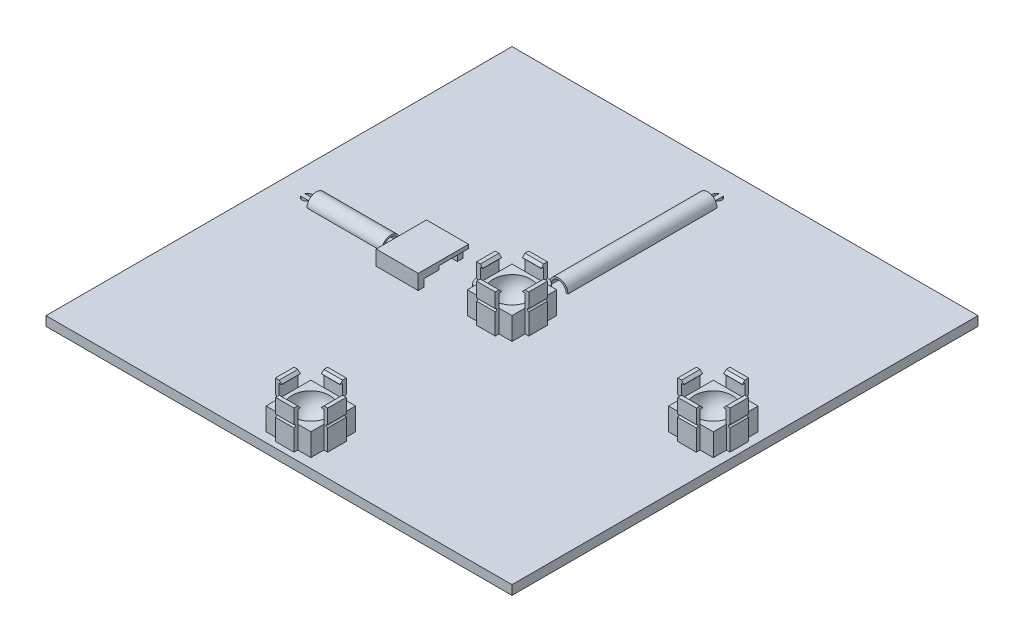
SolidWorks part; units mm, degrees
ref_plane "Front Plane" through (0, 0, 0) normal (0, 0, 1) x (1, 0, 0)
ref_plane "Top Plane" through (0, 0, 0) normal (0, 1, 0) x (1, 0, 0)
ref_plane "Right Plane" through (0, 0, 0) normal (1, 0, 0) x (0, 0, -1)
sketch "Sketch1" plane through (0, 0, 0) normal (0, 1, 0) x (1, 0, 0)
  line L1 (0, 0) -> (250, 0)
  line L2 (0, 0) -> (0, 250)
  line L3 (0, 250) -> (250, 250)
  line L4 (250, 0) -> (250, 250)
  dimension "D1" = 250
  dimension "D2" = 250
extrude "Boss-Extrude1" add sketch "Sketch1" along normal blind 5
sketch "Sketch2" plane through (0, 5, 0) normal (0, 1, 0) x (1, 0, 0)
  line L1 (113, 113) -> (137, 113)
  line L2 (113, 113) -> (113, 137)
  line L3 (113, 137) -> (137, 137)
  line L4 (137, 113) -> (137, 137)
  line L5 (113, 113) -> (137, 137) construction
  line L6 (113, 137) -> (137, 113) construction
  line L7 (0, 250) -> (0, 0) construction
  line L8 (250, 250) -> (0, 250) construction
  line L10 (221, 137) -> (221, 113)
  line L11 (221, 113) -> (245, 113)
  line L12 (245, 113) -> (245, 137)
  line L13 (245, 137) -> (221, 137)
  line L19 (137, 29.0789) -> (113, 29.0789)
  line L20 (113, 29.0789) -> (113, 5.0789)
  line L21 (113, 5.0789) -> (137, 5.0789)
  line L22 (137, 5.0789) -> (137, 29.0789)
  point P0 (125, 125)
  dimension "D1" = 24
  dimension "D2" = 24
  dimension "D3" = 125
  dimension "D4" = 125
extrude "Boss-Extrude2" add sketch "Sketch2" along normal blind 12
sketch "Sketch4" plane through (0, 17, 0) normal (0, 1, 0) x (1, 0, 0)
  line L0 (125, 135) -> (125, 115)
  line L1 (125, 7) -> (125, 27)
  line L3 (233, 135) -> (233, 115)
  arc A0 (125, 135) -> (125, 115) centre (125, 125) ccw
  arc A2 (125, 27) -> (125, 7) centre (125, 17) ccw
  arc A3 (233, 115) -> (233, 135) centre (233, 125) ccw
revolve "Cut-Revolve1" cut sketch "Sketch4" angle 360 about L0 region at (120.7559, 17, -125)
revolve "Cut-Revolve2" cut sketch "Sketch4<3>" angle 360 about L3
sketch "Sketch4<3>" plane through (0, 17, 0) normal (0, 1, 0) x (1, 0, 0) same geometry as "Sketch4"
revolve "Cut-Revolve3" cut sketch "Sketch4<4>" angle 360 about L1
sketch "Sketch4<4>" plane through (0, 17, 0) normal (0, 1, 0) x (1, 0, 0) same geometry as "Sketch4"
sketch "Sketch5" plane through (0, 5, 0) normal (0, 1, 0) x (1, 0, 0)
  line L8 (125, 137) -> (130, 137)
  line L9 (137, 137) -> (113, 137) construction
  line L10 (137, 137) -> (113, 137) construction
  line L11 (130, 137) -> (130, 139)
  line L12 (130, 139) -> (120, 139)
  line L13 (120, 139) -> (120, 137)
  line L14 (120, 137) -> (125, 137)
  line L15 (120, 113) -> (125, 113)
  line L16 (120, 111) -> (120, 113)
  line L17 (130, 111) -> (120, 111)
  line L18 (130, 113) -> (130, 111)
  line L19 (125, 113) -> (130, 113)
  line L21 (113, 29.0789) -> (113, 5.0789) construction
  line L22 (137, 5.0789) -> (137, 29.0789) construction
  line L24 (125, 29.0789) -> (130, 29.0789)
  line L25 (130, 29.0789) -> (130, 31.0789)
  line L26 (130, 31.0789) -> (120, 31.0789)
  line L27 (120, 31.0789) -> (120, 29.0789)
  line L28 (120, 29.0789) -> (125, 29.0789)
  line L29 (120, 5.0789) -> (125, 5.0789)
  line L30 (120, 3.0789) -> (120, 5.0789)
  line L31 (130, 3.0789) -> (120, 3.0789)
  line L32 (130, 5.0789) -> (130, 3.0789)
  line L33 (125, 5.0789) -> (130, 5.0789)
  line L36 (113, 130) -> (113, 125)
  line L37 (111, 130) -> (113, 130)
  line L38 (111, 120) -> (111, 130)
  line L39 (113, 120) -> (111, 120)
  line L40 (113, 125) -> (113, 120)
  line L41 (137, 125) -> (137, 120)
  line L42 (137, 120) -> (139, 120)
  line L43 (139, 120) -> (139, 130)
  line L44 (139, 130) -> (137, 130)
  line L45 (137, 130) -> (137, 125)
  line L46 (220.9211, 130) -> (220.9211, 125)
  line L47 (218.9211, 130) -> (220.9211, 130)
  line L48 (218.9211, 120) -> (218.9211, 130)
  line L49 (220.9211, 120) -> (218.9211, 120)
  line L50 (220.9211, 125) -> (220.9211, 120)
  line L51 (244.9211, 125) -> (244.9211, 120)
  line L52 (244.9211, 120) -> (246.9211, 120)
  line L53 (246.9211, 120) -> (246.9211, 130)
  line L54 (246.9211, 130) -> (244.9211, 130)
  line L55 (244.9211, 130) -> (244.9211, 125)
  line L56 (137, 12.0789) -> (137, 17.0789)
  line L57 (139, 12.0789) -> (137, 12.0789)
  line L58 (139, 22.0789) -> (139, 12.0789)
  line L59 (137, 22.0789) -> (139, 22.0789)
  line L60 (137, 17.0789) -> (137, 22.0789)
  line L61 (113, 17.0789) -> (113, 22.0789)
  line L62 (113, 22.0789) -> (111, 22.0789)
  line L63 (111, 22.0789) -> (111, 12.0789)
  line L64 (111, 12.0789) -> (113, 12.0789)
  line L65 (113, 12.0789) -> (113, 17.0789)
  line L66 (237.9211, 137) -> (232.9211, 137)
  line L67 (237.9211, 139) -> (237.9211, 137)
  line L68 (227.9211, 139) -> (237.9211, 139)
  line L69 (227.9211, 137) -> (227.9211, 139)
  line L70 (232.9211, 137) -> (227.9211, 137)
  line L71 (232.9211, 113) -> (227.9211, 113)
  line L72 (227.9211, 113) -> (227.9211, 111)
  line L73 (227.9211, 111) -> (237.9211, 111)
  line L74 (237.9211, 111) -> (237.9211, 113)
  line L75 (237.9211, 113) -> (232.9211, 113)
extrude "Boss-Extrude3" add sketch "Sketch5" along normal blind 19
sketch "Sketch8" plane through (120, 0, 0) normal (-1, 0, 0) x (0, 0, 1)
  line L0 (-3.0789, 24) -> (-6.5789, 24)
  line L1 (-3.0789, 24) -> (-3.0789, 25.5)
  line L2 (-3.0789, 25.5) -> (-5.0789, 25.5)
  line L3 (-5.0789, 25.5) -> (-6.5789, 24)
  line L8 (-29.0789, 25.5) -> (-27.5789, 24)
  line L9 (-31.0789, 25.5) -> (-29.0789, 25.5)
  line L10 (-31.0789, 24) -> (-31.0789, 25.5)
  line L11 (-31.0789, 24) -> (-27.5789, 24)
  line L12 (-111, 24) -> (-114.5, 24)
  line L13 (-111, 24) -> (-111, 25.5)
  line L14 (-111, 25.5) -> (-113, 25.5)
  line L15 (-113, 25.5) -> (-114.5, 24)
  line L16 (-137, 25.5) -> (-135.5, 24)
  line L17 (-139, 25.5) -> (-137, 25.5)
  line L18 (-139, 24) -> (-139, 25.5)
  line L19 (-139, 24) -> (-135.5, 24)
extrude "Boss-Extrude5" add sketch "Sketch8" against normal blind 10
sketch "Sketch9" plane through (0, 0, -130) normal (0, 0, -1) x (-1, 0, 0)
  line L0 (-111, 24) -> (-114.5, 24)
  line L1 (-111, 24) -> (-111, 25.5)
  line L2 (-111, 25.5) -> (-113, 25.5)
  line L3 (-113, 25.5) -> (-114.5, 24)
  line L8 (-137, 25.5) -> (-135.5, 24)
  line L9 (-139, 25.5) -> (-137, 25.5)
  line L10 (-139, 24) -> (-139, 25.5)
  line L11 (-139, 24) -> (-135.5, 24)
  line L12 (-218.9211, 24) -> (-222.4211, 24)
  line L13 (-218.9211, 24) -> (-218.9211, 25.5)
  line L14 (-218.9211, 25.5) -> (-220.9211, 25.5)
  line L15 (-220.9211, 25.5) -> (-222.4211, 24)
  line L16 (-244.9211, 25.5) -> (-243.4211, 24)
  line L17 (-246.9211, 25.5) -> (-244.9211, 25.5)
  line L18 (-246.9211, 24) -> (-246.9211, 25.5)
  line L19 (-246.9211, 24) -> (-243.4211, 24)
extrude "Boss-Extrude6" add sketch "Sketch9" against normal blind 10
sketch "Sketch10" plane through (237.9211, 0, 0) normal (1, 0, 0) x (0, 0, -1)
  line L0 (139, 24) -> (135.5, 24)
  line L1 (135.5, 24) -> (137, 25.5)
  line L2 (137, 25.5) -> (139, 25.5)
  line L3 (139, 25.5) -> (139, 24)
  line L8 (111, 25.5) -> (111, 24)
  line L9 (113, 25.5) -> (111, 25.5)
  line L10 (114.5, 24) -> (113, 25.5)
  line L11 (111, 24) -> (114.5, 24)
extrude "Boss-Extrude7" add sketch "Sketch10" against normal blind 10
sketch "Sketch11" plane through (0, 0, -12.0789) normal (0, 0, 1) x (1, 0, 0)
  line L0 (139, 24) -> (135.5, 24)
  line L1 (135.5, 24) -> (137, 25.5)
  line L2 (137, 25.5) -> (139, 25.5)
  line L3 (139, 25.5) -> (139, 24)
  line L6 (111, 25.5) -> (111, 24)
  line L7 (113, 25.5) -> (111, 25.5)
  line L8 (114.5, 24) -> (113, 25.5)
  line L9 (111, 24) -> (114.5, 24)
extrude "Boss-Extrude8" add sketch "Sketch11" against normal blind 10
sketch "Sketch12" plane through (0, 0, -12.0789) normal (0, 0, 1) x (1, 0, 0)
  line L0 (139, 25.5) -> (139, 5) construction
  line L1 (111, 25.5) -> (111, 5) construction
  circle A0 centre (139, 17) radius 0.75
  circle A1 centre (111, 17) radius 0.75
extrude "Cut-Extrude1" cut sketch "Sketch12" against normal through all
sketch "Sketch13" plane through (120, 0, 0) normal (-1, 0, 0) x (0, 0, 1)
  line L0 (-111, 25.5) -> (-111, 5) construction
  line L1 (-139, 25.5) -> (-139, 5) construction
  circle A0 centre (-111, 17) radius 0.75
  circle A1 centre (-139, 17) radius 0.75
extrude "Cut-Extrude2" cut sketch "Sketch13" against normal through all
sketch "Sketch14" plane through (0, 0, -130) normal (0, 0, -1) x (-1, 0, 0)
  line L0 (-218.9211, 25.5) -> (-218.9211, 5) construction
  line L1 (-246.9211, 25.5) -> (-246.9211, 5) construction
  circle A0 centre (-218.9211, 17) radius 0.75
  circle A1 centre (-246.9211, 17) radius 0.75
extrude "Cut-Extrude3" cut sketch "Sketch14" against normal through all
sketch "Sketch15" plane through (130, 0, 0) normal (1, 0, 0) x (0, 0, -1)
  line L0 (31.0789, 25.5) -> (31.0789, 5) construction
  line L1 (3.0789, 25.5) -> (3.0789, 5) construction
  circle A0 centre (31.0789, 17) radius 0.75
  circle A1 centre (3.0789, 17) radius 0.75
extrude "Cut-Extrude4" cut sketch "Sketch15" against normal through all
fillet "Fillet1" radius 0.1 12 edges at (232.9211, 24, -135.5) (243.4211, 24, -125) (232.9211, 24, -114.5) (222.4211, 24, -125) (114.5, 24, -125) (125, 24, -135.5) (125, 24, -114.5) (135.5, 24, -125) (135.5, 24, -17.0789) (125, 24, -6.5789) (114.5, 24, -17.0789) (125, 24, -27.5789)
sketch "Sketch17" plane through (0, 0, 0) normal (0, -1, 0) x (1, 0, 0)
  line L0 (124.65, -235) -> (125.35, -235) construction
  line L1 (250, -250) -> (0, -250) construction
  line L2 (125, -125) -> (0, -250)
  line L3 (125, -250) -> (125, -235)
  line L4 (124.65, -232.7) -> (125.35, -232.7)
  line L5 (124.65, -237.3) -> (125.35, -237.3)
  line L6 (15, -125.35) -> (15, -124.65) construction
  line L7 (17.3, -125.35) -> (17.3, -124.65)
  line L8 (12.7, -125.35) -> (12.7, -124.65)
  arc A0 (124.65, -232.7) -> (124.65, -237.3) centre (124.65, -235) ccw
  arc A1 (125.35, -237.3) -> (125.35, -232.7) centre (125.35, -235) ccw
  arc A2 (17.3, -125.35) -> (12.7, -125.35) centre (15, -125.35) cw
  arc A3 (12.7, -124.65) -> (17.3, -124.65) centre (15, -124.65) cw
  point P9 (125, -235)
  point P16 (15, -125)
  dimension "D1" = 0.7
  dimension "D2" = 4.6
extrude "Cut-Extrude5" cut sketch "Sketch17" against normal blind 2.3 contours L5 A1 L4 A0 | A3 L8 A2 L7 region at (125, 0, -232.7702) region at (15, 0, -125)
sketch "Sketch18" plane through (0, 2.3, 0) normal (0, -1, 0) x (1, 0, 0)
  line L0 (0, -250) -> (125, -125)
  line L1 (17.1564, -123.85) -> (12.8436, -123.85)
  line L2 (17.1564, -126.15) -> (12.8436, -126.15)
  line L3 (123.85, -232.8436) -> (123.85, -237.1564)
  line L4 (126.15, -232.8436) -> (126.15, -237.1564)
  line L6 (123.85, -231.5086) -> (123.85, -238.4914) construction
  line L7 (126.15, -231.5086) -> (126.15, -238.4914) construction
  line L8 (124.65, -232.7) -> (124.65, -237.3) construction
  line L9 (125.35, -232.7) -> (125.35, -237.3) construction
  arc A0 (123.85, -232.8436) -> (123.85, -237.1564) centre (124.65, -235) ccw
  arc A1 (126.15, -237.1564) -> (126.15, -232.8436) centre (125.35, -235) ccw
  arc A2 (12.8436, -123.85) -> (17.1564, -123.85) centre (15, -124.65) cw
  arc A3 (124.65, -232.7) -> (124.65, -237.3) centre (124.65, -235) ccw construction
  arc A4 (125.35, -237.3) -> (125.35, -232.7) centre (125.35, -235) ccw construction
  arc A5 (123.85, -238.4914) -> (123.85, -231.5086) centre (125.35, -235) ccw construction
  arc A6 (126.15, -231.5086) -> (126.15, -238.4914) centre (124.65, -235) ccw construction
  arc A7 (17.1564, -126.15) -> (12.8436, -126.15) centre (15, -125.35) cw
  arc M2 (125.35, -237.3) -> (125.35, -232.7) centre (125.35, -235) ccw
  arc M4 (124.65, -232.7) -> (124.65, -237.3) centre (124.65, -235) ccw
  dimension "D1" = 1.5
extrude "Cut-Extrude6" cut sketch "Sketch18" against normal through all contours L3 M4 | L4 M2 | A7 L2 | A2 L1 region at (15, 2.3, -123.2293) region at (15, 2.3, -126.7707) region at (123.2293, 2.3, -235) region at (126.7707, 2.3, -235)
sketch "Sketch19" plane through (0, 0, 0) normal (0, 0, 1) x (1, 0, 0)
  line L0 (120, 5) -> (130, 5) construction
  line L1 (120, 5) -> (121, 5)
  line L2 (129, 5) -> (130, 5)
  arc A0 (130, 5) -> (120, 5) centre (125, 5) ccw
  arc A1 (129, 5) -> (121, 5) centre (125, 5) ccw
extrude "Boss-Extrude9" add sketch "Sketch19" against normal blind 80 from offset 150 offset against normal yes
sketch "Sketch20" plane through (0, 0, 0) normal (1, 0, 0) x (0, 0, -1)
  line L0 (0, 5) -> (250, 5) construction
  line L1 (120, 5) -> (121, 5)
  line L2 (129, 5) -> (130, 5)
  arc A0 (130, 5) -> (120, 5) centre (125, 5) ccw
  arc A1 (129, 5) -> (121, 5) centre (125, 5) ccw
extrude "Boss-Extrude10" add sketch "Sketch20" along normal blind 40 from offset 20
sketch "Sketch21" plane through (0, 5, 0) normal (0, 1, 0) x (1, 0, 0)
  line L0 (85.2046, 138.5) -> (65.6046, 138.5)
  line L1 (85.2046, 135.5) -> (68.6046, 135.5)
  line L2 (68.6046, 135.5) -> (68.6046, 114.5)
  line L3 (68.6046, 114.5) -> (85.2046, 114.5)
  line L4 (65.6046, 138.5) -> (65.6046, 111.5)
  line L5 (65.6046, 111.5) -> (85.2046, 111.5)
  line L6 (85.2046, 138.5) -> (85.2046, 135.5)
  line L8 (85.2046, 114.5) -> (85.2046, 122.5)
  line L9 (85.2046, 122.5) -> (88.2046, 122.5)
  line L10 (88.2046, 122.5) -> (88.2046, 111.5)
  line L11 (88.2046, 111.5) -> (85.2046, 111.5)
  dimension "D1" = 3
extrude "Boss-Extrude11" add sketch "Sketch21" along normal blind 6
sketch "Sketch22" plane through (0, 11, 0) normal (0, 1, 0) x (1, 0, 0)
  line L1 (65.6046, 138.5) -> (88.2046, 138.5)
  line L2 (65.6046, 138.5) -> (65.6046, 111.5)
  line L3 (65.6046, 111.5) -> (88.2046, 111.5)
  line L4 (88.2046, 138.5) -> (88.2046, 111.5)
extrude "Boss-Extrude12" add sketch "Sketch22" along normal blind 2
sketch "Sketch23" plane through (0, 13, 0) normal (0, 1, 0) x (1, 0, 0)
  line L0 (88.2046, 122.5) -> (85.2046, 122.5)
  line L1 (85.2046, 122.5) -> (85.2046, 114.5)
  line L2 (85.2046, 114.5) -> (88.2046, 114.5)
  line L3 (88.2046, 111.5) -> (88.2046, 138.5) construction
  line L4 (88.2046, 114.5) -> (88.2046, 122.5)
extrude "Cut-Extrude7" cut sketch "Sketch23" against normal blind 4 from offset 4 offset against normal yes
sketch "Sketch24" plane through (65.6046, 0, 0) normal (-1, 0, 0) x (0, 0, 1)
  line L0 (-138.5, 5) -> (-111.5, 5) construction
  line L1 (-127, 5) -> (-123, 5)
  arc A0 (-123, 5) -> (-127, 5) centre (-125, 5) ccw
extrude "Cut-Extrude8" cut sketch "Sketch24" against normal blind 6
sketch "Sketch26" plane through (0, 5, 0) normal (0, 1, 0) x (1, 0, 0)
  line L0 (111, 120) -> (111, 130) construction
  line L1 (111, 130) -> (111, 128)
  line L2 (111, 122) -> (111, 120)
  arc A0 (111, 130) -> (111, 120) centre (111, 125) ccw
  arc A1 (111, 128) -> (111, 122) centre (111, 125) ccw
extrude "Boss-Extrude13" add sketch "Sketch26" along normal blind 3 from offset 5
sketch "Sketch27" plane through (0, 5, 0) normal (0, 1, 0) x (1, 0, 0)
  line L0 (130, 139) -> (120, 139) construction
  line L1 (120, 139) -> (122, 139)
  line L2 (128, 139) -> (130, 139)
  arc A0 (130, 139) -> (120, 139) centre (125, 139) ccw
  arc A1 (128, 139) -> (122, 139) centre (125, 139) ccw
extrude "Boss-Extrude14" add sketch "Sketch27" along normal blind 3 from offset 5
